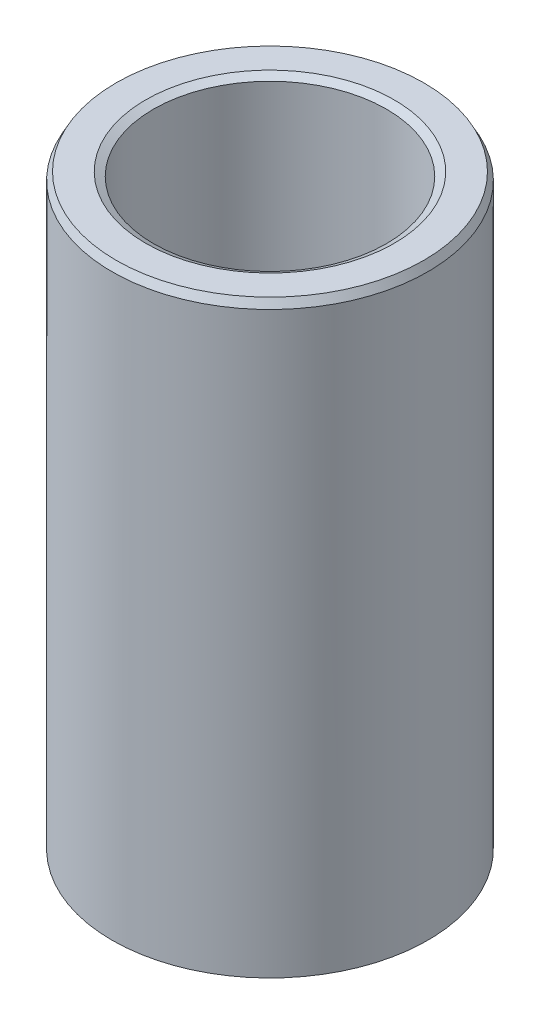
SolidWorks part; units mm, degrees
ref_plane "Front Plane" through (0, 0, 0) normal (0, 0, 1) x (1, 0, 0)
ref_plane "Top Plane" through (0, 0, 0) normal (0, 1, 0) x (1, 0, 0)
ref_plane "Right Plane" through (0, 0, 0) normal (1, 0, 0) x (0, 0, -1)
sketch "Sketch1" plane through (0, 0, 0) normal (0, 1, 0) x (1, 0, 0)
  circle A0 centre (0, 0) radius 32.5
  dimension "SLEEVE_OD" = 65
extrude "Boss-Extrude1" add sketch "Sketch1" along normal blind 121.5679
sketch "Sketch2" plane through (0, 0, 0) normal (0, 1, 0) x (1, 0, 0)
  circle A0 centre (0, 0) radius 23.9731
  dimension "BORE_D" = 47.9462
extrude "Cut-Extrude1" cut sketch "Sketch2" along normal through all
chamfer "Chamfer1" distance 1.5988 angle 28.209 4 edges at (0, 121.5679, 23.9731) (0, 0, 23.9731) (0, 0, 32.5) (0, 121.5679, 32.5) first distance on face at (0, 121.5679, 23.9731) first distance on face at (0, 0, 23.9731) first distance on face at (0, 121.5679, 32.5)
